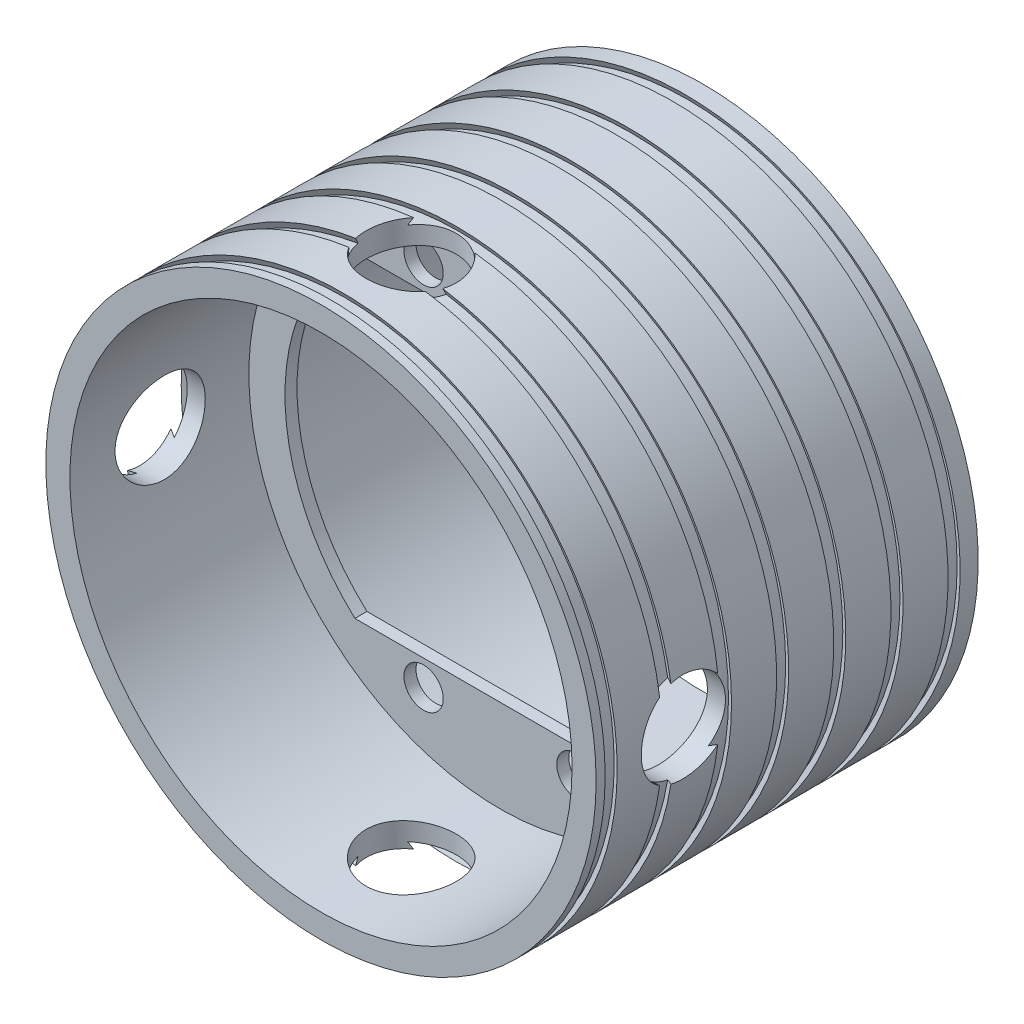
SolidWorks part; units mm, degrees
material "6061 Alloy"
ref_plane "Front Plane" through (0, 0, 0) normal (0, 0, 1) x (1, 0, 0)
ref_plane "Top Plane" through (0, 0, 0) normal (0, 1, 0) x (1, 0, 0)
ref_plane "Right Plane" through (0, 0, 0) normal (1, 0, 0) x (0, 0, -1)
sketch "Sketch1" plane through (0, 0, 0) normal (0, 0, 1) x (1, 0, 0)
  line L0 (0, -35.7344) -> (0, 35.7344) construction
  line L1 (-35.7344, 0) -> (35.7344, 0) construction
  line L2 (24.1131, -26.3724) -> (-24.1131, -26.3724)
  line L3 (24.1131, 26.3724) -> (-24.1131, 26.3724)
  circle A0 centre (0, 0) radius 41.7344
  circle A1 centre (0, 0) radius 45.7344
  circle A2 centre (0, 0) radius 35.7344
  arc A3 (37.225, 18.8696) -> (-37.225, 18.8696) centre (0, 0) ccw construction
  dimension "D1" = 6
  dimension "D2" = 4
extrude "Boss-Extrude1" add sketch "Sketch1" against normal up to surface (31.75 mm away) contours A1 A0 region at (-44.4409, 0, 0)
extrude "Boss-Extrude2" add sketch "Sketch1<3>" along normal blind 2 contours A0 A2 | L3 A2 | L2 A2 region at (0, -30.1627, 0) region at (0, 30.1627, 0) region at (-40.554, 0, 0)
sketch "Sketch1<3>" plane through (0, 0, 0) normal (0, 0, 1) x (1, 0, 0) same geometry as "Sketch1"
extrude "Boss-Extrude3" add sketch "Sketch1<4>" along normal blind 31.75 contours A1 A0 region at (-44.4409, 0, 0)
sketch "Sketch1<4>" plane through (0, 0, 0) normal (0, 0, 1) x (1, 0, 0) same geometry as "Sketch1"
ref_plane "Plane4" through (0, 0, 0) normal (1, 0, 0) x (0, 0, -1)
sketch "Sketch2" plane through (0, 0, 0) normal (1, 0, 0) x (0, 0, -1)
  line L0 (-29.25, 45.7344) -> (-29.25, 44.7344) construction
  line L1 (-18.25, 44.7344) -> (-21.25, 44.7344)
  line L2 (-18.25, 44.7344) -> (-18.75, 45.7344)
  line L3 (-18.75, 45.7344) -> (-20.75, 45.7344)
  line L4 (-21.25, 44.7344) -> (-20.75, 45.7344)
  line L6 (-27.75, 44.7344) -> (-30.75, 44.7344)
  line L7 (-27.75, 44.7344) -> (-28.25, 45.7344)
  line L8 (-28.25, 45.7344) -> (-30.25, 45.7344)
  line L9 (-30.75, 44.7344) -> (-30.25, 45.7344)
  line L10 (-31.75, 45.7344) -> (31.75, 45.7344) construction
  line L11 (31.75, 45.7344) -> (-31.75, 45.7344) construction
  line L12 (-18.25, 44.7344) -> (-20.75, 45.7344) construction
  line L13 (-18.75, 45.7344) -> (-21.25, 44.7344) construction
  line L14 (-8.75, 44.7344) -> (-11.75, 44.7344)
  line L15 (-8.75, 44.7344) -> (-9.25, 45.7344)
  line L16 (-9.25, 45.7344) -> (-11.25, 45.7344)
  line L17 (-11.75, 44.7344) -> (-11.25, 45.7344)
  line L18 (-8.75, 44.7344) -> (-11.25, 45.7344) construction
  line L19 (-9.25, 45.7344) -> (-11.75, 44.7344) construction
  line L20 (0.75, 44.7344) -> (-2.25, 44.7344)
  line L21 (0.75, 44.7344) -> (0.25, 45.7344)
  line L22 (0.25, 45.7344) -> (-1.75, 45.7344)
  line L23 (-2.25, 44.7344) -> (-1.75, 45.7344)
  line L24 (0.75, 44.7344) -> (-1.75, 45.7344) construction
  line L25 (0.25, 45.7344) -> (-2.25, 44.7344) construction
  line L26 (10.25, 44.7344) -> (7.25, 44.7344)
  line L27 (10.25, 44.7344) -> (9.75, 45.7344)
  line L28 (9.75, 45.7344) -> (7.75, 45.7344)
  line L29 (7.25, 44.7344) -> (7.75, 45.7344)
  line L30 (10.25, 44.7344) -> (7.75, 45.7344) construction
  line L31 (9.75, 45.7344) -> (7.25, 44.7344) construction
  line L32 (19.75, 44.7344) -> (16.75, 44.7344)
  line L33 (19.75, 44.7344) -> (19.25, 45.7344)
  line L34 (19.25, 45.7344) -> (17.25, 45.7344)
  line L35 (16.75, 44.7344) -> (17.25, 45.7344)
  line L36 (19.75, 44.7344) -> (17.25, 45.7344) construction
  line L37 (19.25, 45.7344) -> (16.75, 44.7344) construction
  line L38 (29.25, 44.7344) -> (26.25, 44.7344)
  line L39 (29.25, 44.7344) -> (28.75, 45.7344)
  line L40 (28.75, 45.7344) -> (26.75, 45.7344)
  line L41 (26.25, 44.7344) -> (26.75, 45.7344)
  line L42 (29.25, 44.7344) -> (26.75, 45.7344) construction
  line L43 (28.75, 45.7344) -> (26.25, 44.7344) construction
  line L44 (-31.75, 45.7344) -> (-31.75, -45.7344) construction
  point P0 (-19.8627, 45.7344)
  point P8 (-9.8627, 45.7344)
  point P18 (0.1373, 45.7344)
  point P23 (10.1373, 45.7344)
  point P28 (20.1373, 45.7344)
  point P33 (30.1373, 45.7344)
  dimension "D1" = 3
  dimension "D3" = 2
  dimension "D4" = 1
  dimension "D5" = 1
  dimension "D2" = 7
ref_axis "Axis1" through (0, 0, 2) along (0, 0, 1)
revolve "Cut-Revolve1" cut sketch "Sketch2" angle 360 about axis through (0, 0, 2) along (0, 0, 1)
sketch "Sketch7" plane through (0, 0, 0) normal (1, 0, 0) x (0, 0, -1)
  line L0 (-31.75, 0) -> (31.75, 0) construction
  line L1 (31.75, -45.7344) -> (31.75, 45.7344) construction
  line L2 (-31.75, 45.7344) -> (-31.75, -45.7344) construction
  circle A0 centre (-16.75, 0) radius 7.5
  dimension "D1" = 15
  dimension "D2" = 15
extrude "Cut-Extrude1" cut sketch "Sketch7" against normal through all both and the other way through all
sketch "Sketch8" plane through (0, 0, 0) normal (0, 1, 0) x (1, 0, 0)
  line L0 (0, -31.75) -> (0, 31.75) construction
  line L3 (-45.7344, -31.75) -> (45.7344, -31.75) construction
  line L4 (41.7344, 31.75) -> (-41.7344, 31.75) construction
  circle A0 centre (0, -16.75) radius 7.5
  dimension "D1" = 15
  dimension "D2" = 15
extrude "Cut-Extrude2" cut sketch "Sketch8" against normal through all both and the other way through all
hole_wizard "1/4 Clearance Hole1" positions "Sketch9" profile "Sketch10" hole size "1/4" standard "ANSI Inch" end condition through all
sketch "Sketch9" plane through (-9.4006, -2.5125, 0) normal (0, 0, -1) x (-1, 0, 0)
  point P0 (3.2994, 33.1344)
  point P1 (-22.1006, 33.1344)
  point P2 (-22.1006, -28.1094)
  point P3 (3.2994, -28.1094)
sketch "Sketch10" plane through (-12.7, 30.6219, 0) normal (1, 0, 0) x (0, 1, 0)
  line L0 (0, 0) -> (0, 31.75)
  line L1 (0, 31.75) -> (3.2639, 31.75)
  line L2 (3.2639, 31.75) -> (3.2639, 0)
  line L5 (3.2639, 0) -> (0, 0)
  line L11 (0, -6.35) -> (0, 107.95) construction
  dimension "Thru Hole Dia." = 6.5278
  dimension "Thru Hole Depth" = 31.75
fillet "Fillet1" radius 1 1 edges at (41.7344, 0, 0)
